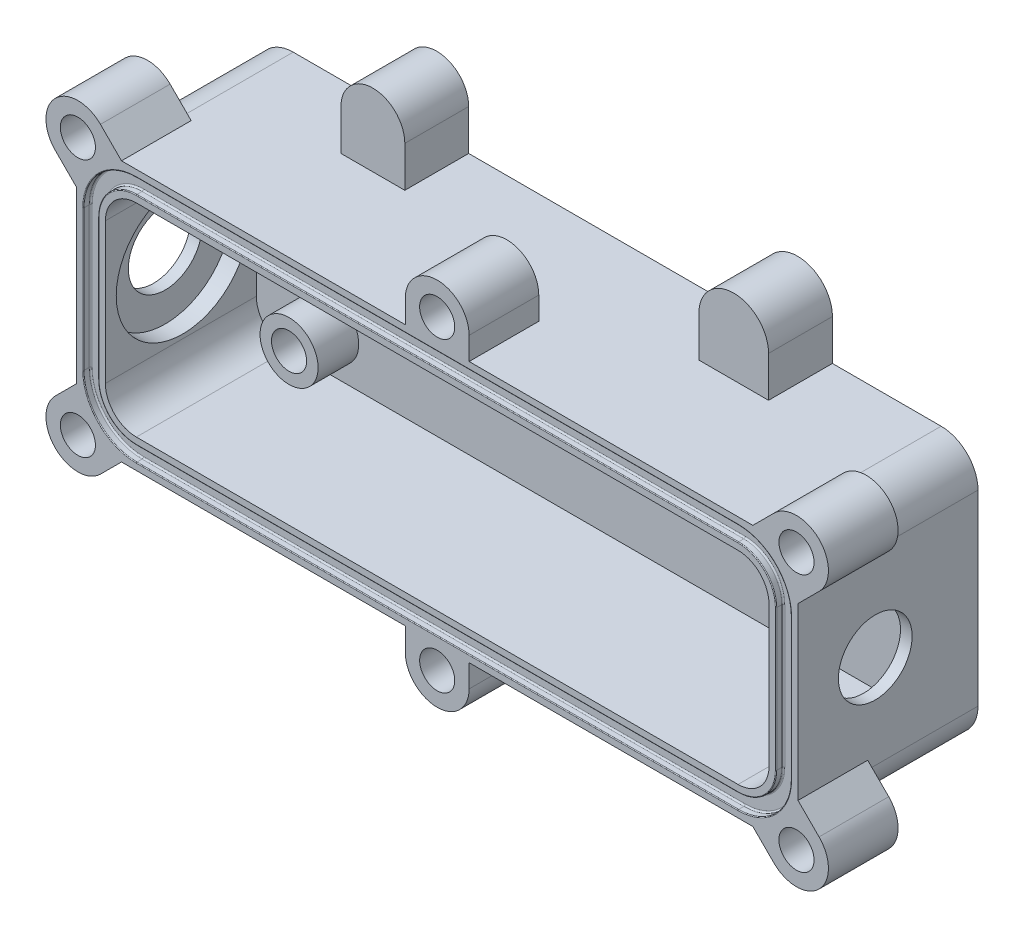
SolidWorks part; units mm, degrees
material "ABS"
ref_plane "X-Y Datum" through (0, 0, 0) normal (0, 0, 1) x (1, 0, 0)
ref_plane "X-Z Datum" through (0, 0, 0) normal (0, 1, 0) x (1, 0, 0)
ref_plane "Y-Z Datum" through (0, 0, 0) normal (1, 0, 0) x (0, 0, -1)
sketch "Sketch1" plane through (0, 0, 0) normal (0, 0, 1) x (1, 0, 0)
  line L1 (-48.9585, 14.1605) -> (48.9585, 14.1605) construction
  line L2 (-48.9585, 14.1605) -> (-48.9585, -14.1605) construction
  line L3 (-48.9585, -14.1605) -> (48.9585, -14.1605) construction
  line L4 (48.9585, 14.1605) -> (48.9585, -14.1605) construction
  line L5 (-48.9585, 14.1605) -> (48.9585, -14.1605) construction
  line L6 (-48.9585, -14.1605) -> (48.9585, 14.1605) construction
  line L7 (-57.15, 17.4625) -> (57.15, 17.4625)
  line L8 (-57.15, 17.4625) -> (-57.15, -17.4625)
  line L9 (-57.15, -17.4625) -> (57.15, -17.4625)
  line L10 (57.15, 17.4625) -> (57.15, -17.4625)
  line L11 (-57.15, 17.4625) -> (57.15, -17.4625) construction
  line L12 (-57.15, -17.4625) -> (57.15, 17.4625) construction
  point P0 (0, 0)
  point P6 (0, 0)
  dimension "D1" = 97.917
  dimension "D2" = 28.321
  dimension "D3" = 114.3
  dimension "D4" = 34.925
extrude "Boss-Extrude1" add sketch "Sketch1" along normal blind 26
shell "Shell1" thickness 5 removed face at (0, 0, 26) outward yes
fillet "Fillet1" radius 5.334 4 edges at (-57.15, 17.4625, 13) (-57.15, -17.4625, 13) (57.15, -17.4625, 13) (57.15, 17.4625, 13)
fillet "Fillet2" radius 6.35 4 edges at (62.15, -22.4625, 10.5) (62.15, 22.4625, 10.5) (-62.15, 22.4625, 10.5) (-62.15, -22.4625, 10.5)
sketch "Sketch2" plane through (0, 0, 26) normal (0, 0, 1) x (1, 0, 0)
  line L20 (-60.9327, 12.1285) -> (-60.9327, -12.1285)
  line L21 (-51.816, -21.2452) -> (51.816, -21.2452)
  line L22 (60.9327, -12.1285) -> (60.9327, 12.1285)
  line L23 (51.816, 21.2452) -> (-51.816, 21.2452)
  line L24 (59.65, -12.1285) -> (59.65, 12.1285)
  line L25 (-51.816, -19.9625) -> (51.816, -19.9625)
  line L26 (-59.65, 12.1285) -> (-59.65, -12.1285)
  line L27 (51.816, 19.9625) -> (-51.816, 19.9625)
  line L28 (59.65, -12.1285) -> (59.65, 12.1285) construction
  line L29 (-51.816, -19.9625) -> (51.816, -19.9625) construction
  line L30 (-59.65, 12.1285) -> (-59.65, -12.1285) construction
  line L31 (51.816, 19.9625) -> (-51.816, 19.9625) construction
  line L32 (51.816, 18.6798) -> (-51.816, 18.6798)
  line L33 (-58.3673, 12.1285) -> (-58.3673, -12.1285)
  line L34 (-51.816, -18.6798) -> (51.816, -18.6798)
  line L35 (58.3673, -12.1285) -> (58.3673, 12.1285)
  arc A16 (-51.816, 21.2452) -> (-60.9327, 12.1285) centre (-51.816, 12.1285) ccw
  arc A17 (-60.9327, -12.1285) -> (-51.816, -21.2452) centre (-51.816, -12.1285) ccw
  arc A18 (51.816, -21.2452) -> (60.9327, -12.1285) centre (51.816, -12.1285) ccw
  arc A19 (60.9327, 12.1285) -> (51.816, 21.2452) centre (51.816, 12.1285) ccw
  arc A20 (59.65, 12.1285) -> (51.816, 19.9625) centre (51.816, 12.1285) ccw
  arc A21 (51.816, -19.9625) -> (59.65, -12.1285) centre (51.816, -12.1285) ccw
  arc A22 (-59.65, -12.1285) -> (-51.816, -19.9625) centre (-51.816, -12.1285) ccw
  arc A23 (-51.816, 19.9625) -> (-59.65, 12.1285) centre (-51.816, 12.1285) ccw
  arc A24 (59.65, 12.1285) -> (51.816, 19.9625) centre (51.816, 12.1285) ccw construction
  arc A25 (51.816, -19.9625) -> (59.65, -12.1285) centre (51.816, -12.1285) ccw construction
  arc A26 (-59.65, -12.1285) -> (-51.816, -19.9625) centre (-51.816, -12.1285) ccw construction
  arc A27 (-51.816, 19.9625) -> (-59.65, 12.1285) centre (-51.816, 12.1285) ccw construction
  arc A28 (-51.816, 18.6798) -> (-58.3673, 12.1285) centre (-51.816, 12.1285) ccw
  arc A29 (-58.3673, -12.1285) -> (-51.816, -18.6798) centre (-51.816, -12.1285) ccw
  arc A30 (51.816, -18.6798) -> (58.3673, -12.1285) centre (51.816, -12.1285) ccw
  arc A31 (58.3673, 12.1285) -> (51.816, 18.6798) centre (51.816, 12.1285) ccw
  dimension "D1" = 2.5
  dimension "D2" = 1.2827
  dimension "D3" = 1.2827
extrude "Cut-Extrude1" cut sketch "Sketch2" against normal blind 1.2446
fillet "Fillet3" radius 0.254 16 edges at (-58.3673, 0, 24.7554) (-56.4485, 16.761, 24.7554) (0, 18.6798, 24.7554) (56.4485, 16.761, 24.7554) (58.3673, 0, 24.7554) (56.4485, -16.761, 24.7554) (0, -18.6798, 24.7554) (-58.2625, 18.575, 24.7554) (0, 21.2452, 24.7554) (58.2625, 18.575, 24.7554) (60.9327, 0, 24.7554) (58.2625, -18.575, 24.7554) (0, -21.2452, 24.7554) (-58.2625, -18.575, 24.7554) (-56.4485, -16.761, 24.7554) (-60.9327, 0, 24.7554)
fillet "Fillet4" radius 0.127 16 edges at (-58.3673, 0, 26) (-56.4485, 16.761, 26) (0, 18.6798, 26) (56.4485, 16.761, 26) (58.3673, 0, 26) (56.4485, -16.761, 26) (0, -18.6798, 26) (-58.2625, 18.575, 26) (0, 21.2452, 26) (58.2625, 18.575, 26) (60.9327, 0, 26) (58.2625, -18.575, 26) (0, -21.2452, 26) (-58.2625, -18.575, 26) (-56.4485, -16.761, 26) (-60.9327, 0, 26)
sketch "Sketch4" plane through (0, 0, 26) normal (0, 0, 1) x (1, 0, 0)
  line L0 (51.816, -12.1285) -> (61.8878, -22.2003) construction
  line L1 (54.3718, -22.4625) -> (57.9987, -26.0894)
  line L2 (62.15, -16.1125) -> (62.15, 16.1125) construction
  line L3 (-55.8, -22.4625) -> (55.8, -22.4625) construction
  line L4 (62.15, -14.6843) -> (65.7769, -18.3112)
  circle A2 centre (61.8878, -22.2003) radius 3.025
  circle A4 centre (61.8878, -22.2003) radius 5.5
  arc A5 (51.816, -21.3722) -> (61.0597, -12.1285) centre (51.816, -12.1285) ccw construction
  arc A6 (51.816, -21.3722) -> (61.0597, -12.1285) centre (51.816, -12.1285) ccw
  point P8 (58.3523, -18.6648)
  arc M7 (61.0597, -12.1285) -> (51.816, -21.3722) centre (51.816, -12.1285) cw
  line M10 (-55.8, -22.4625) -> (55.8, -22.4625)
  arc M11 (55.8, -22.4625) -> (62.15, -16.1125) centre (55.8, -16.1125) ccw
  line M12 (62.15, -16.1125) -> (62.15, 16.1125)
  dimension "D1" = 6.05
  dimension "D2" = 11
  dimension "D3" = 5
extrude "Boss-Extrude3" add sketch "Sketch4" against normal blind 12 contours A4 L1 M11 M10 | A4 A2 M11 | A2 M11 | A2 L0 M11 | L0 A2 M11 | L0 A6 A4 A2 M11 | L0 A2 A4 M7 M11 | A4 L4 M12 M11 region at (60.3617, -18.2284, 26) region at (57.9159, -20.6742, 26) region at (60.4971, -19.8932, 26) region at (59.5807, -20.8096, 26) region at (63.113, -16.2721, 26) region at (64.0379, -17.3074, 26) region at (55.9596, -23.4255, 26) region at (62.0092, -22.3217, 26)
sketch "Sketch5" plane through (0, 0, 26) normal (0, 0, 1) x (1, 0, 0)
  circle A2 centre (61.8878, -22.2003) radius 3.025 construction
  circle A3 centre (61.8878, -22.2003) radius 3.025
  dimension "D1" = 6.05
extrude "Cut-Extrude3" cut sketch "Sketch5" against normal blind 9
mirror "Mirror1" about plane through (0, 0, 0) normal (0, 1, 0) of "Cut-Extrude3", "Boss-Extrude3"
mirror "Mirror2" about plane through (0, 0, 0) normal (1, 0, 0) of "Mirror1", "Cut-Extrude3", "Boss-Extrude3"
sketch "Sketch6" plane through (0, 0, 26) normal (0, 0, 1) x (1, 0, 0)
  line L0 (0, -22.4625) -> (0, -26.3722)
  line L1 (-54.3718, -22.4625) -> (54.3718, -22.4625) construction
  line L2 (51.816, -21.3722) -> (-51.816, -21.3722) construction
  line L3 (51.816, -21.3722) -> (-51.816, -21.3722)
  line L4 (-5.5, -26.3722) -> (-5.5, -22.4625)
  line L5 (5.5, -26.3722) -> (5.5, -22.4625)
  circle A0 centre (0, -26.3722) radius 5.5
  circle A1 centre (0, -26.3722) radius 3.025
  line M18 (-54.3718, -22.4625) -> (54.3718, -22.4625)
  dimension "D2" = 11
  dimension "D3" = 6.05
  dimension "D1" = 5
extrude "Boss-Extrude4" add sketch "Sketch6" against normal blind 12 contours A1 A0 M18 | A1 | A0 L5 M18 | A0 L4 M18 | A0 L3 M18 region at (2.0785, -24.2937, 26) region at (1.9342, -22.6073, 26) region at (0, -21.9616, 26) region at (-5.0261, -23.4086, 26) region at (5.0261, -23.4086, 26)
sketch "Sketch7" plane through (0, 0, 26) normal (0, 0, 1) x (1, 0, 0)
  circle A0 centre (0, -26.3722) radius 3.025 construction
  circle A1 centre (0, -26.3722) radius 3.025
  dimension "D1" = 6.05
extrude "Cut-Extrude4" cut sketch "Sketch7" against normal blind 9
mirror "Mirror3" about plane through (0, 0, 0) normal (0, 1, 0) of "Cut-Extrude4", "Boss-Extrude4"
sketch "Sketch9" plane through (62.15, 0, 0) normal (1, 0, 0) x (0, 0, -1)
  line L0 (-26, 0) -> (5, 0) construction
  line L1 (-26, -14.6843) -> (-26, 14.6843) construction
  line L2 (5, -16.1125) -> (5, 16.1125) construction
  line L3 (0, -12.1285) -> (0, 12.1285) construction
  circle A0 centre (-12.7, 0) radius 6.35
  circle A1 centre (-12.7, 0) radius 11.43
  dimension "D1" = 12.7
  dimension "D3" = 22.86
  dimension "D2" = 12.7
extrude "Cut-Extrude5" cut sketch "Sketch9" against normal blind 6 contours L0 A0 | A0 L0 region at (62.15, -2.695, 12.7) region at (62.15, 2.695, 12.7)
sketch "Sketch10" plane through (0, 0, 0) normal (0, 0, 1) x (1, 0, 0)
  circle A0 centre (-44.5135, 10.4775) radius 3.025
  circle A1 centre (-44.5135, -10.4775) radius 3.025
  circle A2 centre (44.1265, -0.0975) radius 3.025
  circle A3 centre (-44.5135, 10.4775) radius 5
  circle A4 centre (-44.5135, -10.4775) radius 5
  circle A5 centre (44.1265, -0.0975) radius 5
  point P0 (-44.5135, 10.4775)
  point P1 (-44.5135, -10.4775)
  point P3 (44.1265, -0.0975)
  dimension "D1" = 6.05
  dimension "D2" = 10
extrude "Boss-Extrude5" add sketch "Sketch10" along normal blind 7
sketch "Sketch11" plane through (57.15, 0, 0) normal (-1, 0, 0) x (0, 0, 1)
  circle A0 centre (12.7, 0) radius 11.43 construction
  circle A1 centre (12.7, 0) radius 11.43
  dimension "D1" = 22.86
extrude "Cut-Extrude6" cut sketch "Sketch11" against normal blind 3
mirror "Mirror4" about plane through (0, 0, 0) normal (1, 0, 0) of "Cut-Extrude6", "Cut-Extrude5"
sketch "Sketch12" plane through (0, 0, -5) normal (0, 0, -1) x (-1, 0, 0)
  line L0 (-62.15, 22.4625) -> (0, 22.4625)
  line L1 (-62.15, 22.4625) -> (62.15, 22.4625)
  line L2 (-62.15, 22.4625) -> (-62.15, -22.4625) construction
  line L3 (-62.15, -22.4625) -> (62.15, -22.4625) construction
  line L4 (62.15, 22.4625) -> (62.15, -22.4625) construction
  line L5 (-62.15, 22.4625) -> (62.15, -22.4625) construction
  line L6 (-62.15, -22.4625) -> (62.15, 22.4625) construction
  line L7 (0, 22.4625) -> (-31.075, 22.4625)
  line L8 (-31.075, 22.4625) -> (-31.075, 29.4625) construction
  line L9 (0, 22.4625) -> (62.15, 22.4625)
  line L10 (31.075, 22.4625) -> (31.075, 29.4625) construction
  line L11 (-37.075, 29.4625) -> (-37.075, 22.4625)
  line L12 (-25.075, 29.4625) -> (-25.075, 22.4625)
  line L13 (25.575, 29.4625) -> (25.575, 22.4625)
  line L14 (36.575, 29.4625) -> (36.575, 22.4625)
  circle A0 centre (-31.075, 29.4625) radius 3.025
  circle A1 centre (31.075, 29.4625) radius 3.025
  circle A2 centre (-31.075, 29.4625) radius 6
  circle A3 centre (31.075, 29.4625) radius 5.5
  dimension "D1" = 6.05
  dimension "D2" = 12
  dimension "D3" = 11
  dimension "D4" = 7
extrude "Boss-Extrude6" add sketch "Sketch12" against normal blind 11 contours A2 L11 L1 L7 L12 | A2 A0 | A0 | A3 L13 L9 L14 | A3 A1 | A1 region at (36.9361, 25.9625, -5) region at (-25.7054, 25.9625, -5) region at (31.075, 35.2928, -5) region at (-31.075, 34.8069, -5) region at (31.075, 29.4625, -5) region at (-31.075, 29.4625, -5)
sketch "Sketch13" plane through (0, 0, -5) normal (0, 0, -1) x (-1, 0, 0)
  circle A1 centre (31.075, 29.4625) radius 5.5
  circle A2 centre (31.075, 29.4625) radius 5.5
  circle A3 centre (-31.075, 29.4625) radius 6
  circle A4 centre (-31.075, 29.4625) radius 6
  circle A5 centre (31.075, 29.4625) radius 3.025
  circle A6 centre (31.075, 29.4625) radius 3.025
  circle A7 centre (-31.075, 29.4625) radius 3.025
  circle A8 centre (-31.075, 29.4625) radius 3.025
  dimension "D1" = 0
  dimension "D2" = 0
  dimension "D3" = 0
  dimension "D4" = 0
extrude "Cut-Extrude7" cut sketch "Sketch13" against normal blind 9 contours A8 | A6 region at (-31.075, 29.4625, -5) region at (31.075, 29.4625, -5)
